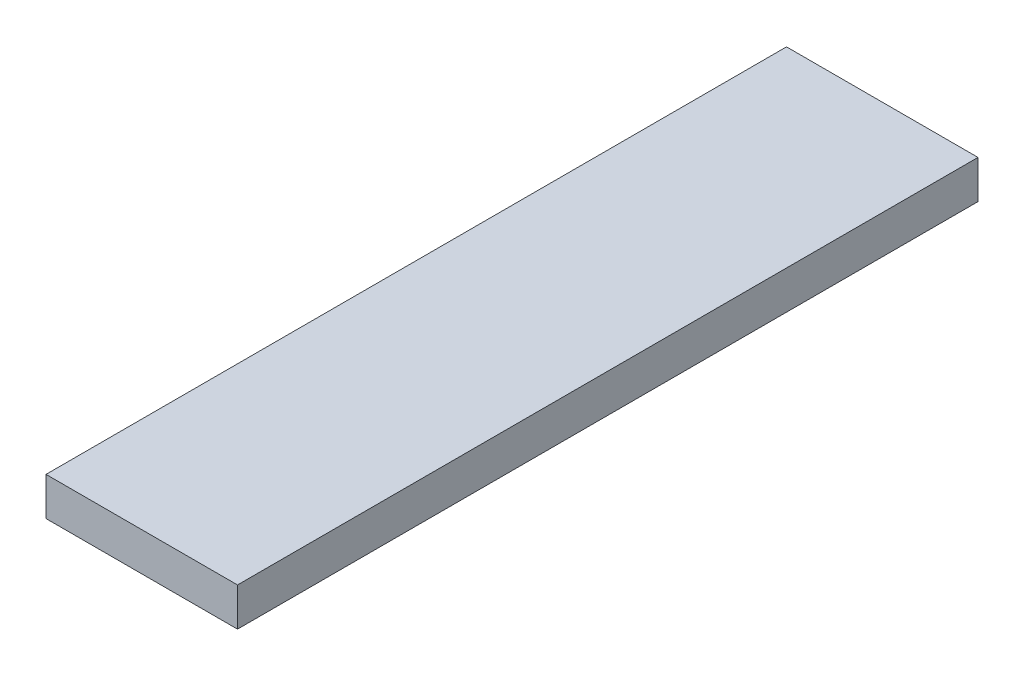
SolidWorks part; units mm, degrees
material "Pine"
ref_plane "Front Plane" through (0, 0, 0) normal (0, 0, 1) x (1, 0, 0)
ref_plane "Top Plane" through (0, 0, 0) normal (0, 1, 0) x (1, 0, 0)
ref_plane "Right Plane" through (0, 0, 0) normal (1, 0, 0) x (0, 0, -1)
sketch "Sketch1" plane through (0, 0, 0) normal (0, 0, 1) x (1, 0, 0)
  line L1 (0, 0) -> (190.5, 0)
  line L2 (0, 0) -> (0, 38.1)
  line L3 (0, 38.1) -> (190.5, 38.1)
  line L4 (190.5, 0) -> (190.5, 38.1)
  dimension "D1" = 190.5
  dimension "D2" = 38.1
extrude "Boss-Extrude1" add sketch "Sketch1" along normal blind 736.6
sketch "Sketch2" plane through (0, 0, 0) normal (0, 0, -1) x (-1, 0, 0)
  line L1 (-190.5, 0) -> (-190.5, 38.1) construction
  line L2 (0, 38.1) -> (0, 0) construction
  line L3 (-95.25, 19.05) -> (-190.5, 19.05) construction
  line L4 (-95.25, 19.05) -> (0, 19.05) construction
  circle A0 centre (-142.875, 19.05) radius 0.8763
  circle A1 centre (-47.625, 19.05) radius 0.8763
  dimension "D1" = 1.7526
sketch "Sketch3" plane through (0, 0, 0) normal (0, -1, 0) x (1, 0, 0)
  line L0 (95.25, 736.6) -> (95.25, 692.15) construction
  line L1 (0, 736.6) -> (190.5, 736.6) construction
  line L2 (95.25, 692.15) -> (95.25, 647.7) construction
  line L3 (190.5, 368.3) -> (0, 368.3) construction
  line L4 (190.5, 736.6) -> (190.5, 0) construction
  line L5 (0, 736.6) -> (0, 0) construction
  line L6 (95.25, 368.3) -> (95.25, 412.75) construction
  line L7 (95.25, 368.3) -> (95.25, 323.85) construction
  circle A0 centre (95.25, 714.375) radius 0.8763
  circle A1 centre (95.25, 669.925) radius 0.8763
  circle A2 centre (95.25, 22.225) radius 0.8763
  circle A3 centre (95.25, 66.675) radius 0.8763
  circle A4 centre (95.25, 346.075) radius 0.8763
  circle A5 centre (95.25, 390.525) radius 0.8763
  dimension "D2" = 1.7526
  dimension "D4" = 1.7526
  dimension "D1" = 88.9
  dimension "D3" = 88.9
equation "\"length\"= 20"
equation "\"length\"= 22"
equation "\"length\"= 36"
equation "\"length\"= 26"
equation "\"length\"= 27"
equation "\"length\"= 28"
equation "\"length\"= 39"
equation "\"length\"= 96"
equation "\"length\"= 30"
equation "\"length\"= 32"
